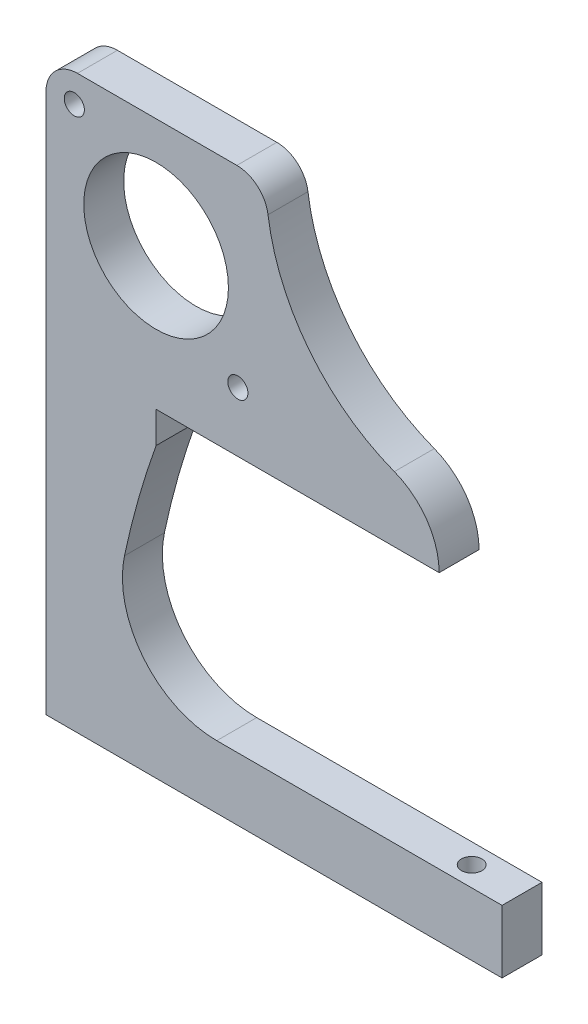
SolidWorks part; units mm, degrees
ref_plane "Front Plane" through (0, 0, 0) normal (0, 0, 1) x (1, 0, 0)
ref_plane "Top Plane" through (0, 0, 0) normal (0, 1, 0) x (1, 0, 0)
ref_plane "Right Plane" through (0, 0, 0) normal (1, 0, 0) x (0, 0, -1)
sketch "Sketch1" plane through (0, 0, 0) normal (0, 0, 1) x (1, 0, 0)
  line L0 (0, 0) -> (35, 0)
  line L1 (62.5, -40) -> (62.5, -43.3792) construction
  line L2 (9.525, -90.8) -> (0, -90.8)
  line L3 (0, -40) -> (0, 0)
  line L4 (30.5, -30.5) -> (4.5, -4.5) construction
  line L5 (4.5, -4.5) -> (30.5, -4.5) construction
  line L6 (4.5, -4.5) -> (4.5, -30.5) construction
  line L7 (4.5, -30.5) -> (30.5, -30.5) construction
  line L8 (30.5, -4.5) -> (30.5, -30.5) construction
  line L9 (0, -40) -> (35, -40) construction
  line L10 (35, -40) -> (35, 0) construction
  line L11 (4.5, -30.5) -> (30.5, -4.5) construction
  line L12 (9.525, -90.8) -> (9.525, -96.7126) construction
  line L13 (0, -90.8) -> (0, -40)
  line L14 (17.5, -40) -> (62.5, -40)
  line L15 (17.5, -40) -> (17.5, -45)
  line L16 (17.5, -45) -> (17.5, -17.5) construction
  line L17 (9.525, -90.8) -> (62.5, -90.8)
  line L18 (62.5, -90.8) -> (62.5, -80.8)
  line L19 (62.5, -80.8) -> (9.8945, -80.8)
  line L20 (62.5, -80.8) -> (72.5, -80.8)
  line L21 (72.5, -80.8) -> (72.5, -90.8)
  line L22 (72.5, -90.8) -> (62.5, -90.8)
  arc A0 (9.8945, -80.8) -> (17.5, -45) centre (145.026, -90.8) cw
  arc A1 (35, 0) -> (55.3806, -29.6446) centre (66.75, 0) ccw
  circle A2 centre (4.5, -4.5) radius 1.6002
  circle A3 centre (17.5, -17.5) radius 11.5
  circle A4 centre (30.5, -30.5) radius 1.6002
  arc A5 (62.5, -40) -> (55.3806, -29.6446) centre (51.4091, -40) ccw
  point P17 (17.5, -17.5)
  dimension "D3" = 3.2004
  dimension "D4" = 40
  dimension "D8" = 23
  dimension "D9" = 31.75
  dimension "D12" = 10
  dimension "D2" = 26
  dimension "D5" = 35
  dimension "D6" = 50.8
  dimension "D7" = 9.525
  dimension "D10" = 5
  dimension "D11" = 45
  dimension "D13" = 10
extrude "Boss-Extrude1" add sketch "Sketch1" along normal blind 6.35 contours L14 A5 A1 L0 L3 L13 L2 L17 L18 L19 A0 L15 A2 A3 A4 region at (17.5, -1.1023, 0)
hole_wizard "#6-32 Tapped Hole1" positions "Sketch4" profile "Sketch3" tap size "#6-32" standard "ANSI Inch"
sketch "Sketch4" plane through (0, -40, 0) normal (0, -1, 0) x (-1, 0, 0)
  line L0 (-17.5, -3.175) -> (-62.5, -3.175) construction
  line L3 (-17.5, -6.35) -> (-17.5, 0) construction
  line L4 (-62.5, -6.35) -> (-62.5, 0) construction
  point P0 (-22.58, -3.175)
  point P2 (-47.98, -3.175)
  dimension "D1" = 5.08
  dimension "D2" = 25.4
sketch "Sketch3" plane through (22.58, -40, 3.175) normal (1, 0, 0) x (0, 0, -1)
  line L0 (0, 0) -> (0, 10.9764)
  line L1 (0, 10.9764) -> (1.625, 10)
  line L2 (1.625, 10) -> (1.625, 0)
  line L5 (1.625, 0) -> (0, 0)
  line L10 (0, 10.9764) -> (-1.625, 10) construction
  line L11 (0, -6.35) -> (0, 107.95) construction
  dimension "Tap Drill Dia." = 3.25
  dimension "Tap Drill Depth" = 10
  dimension "Drill Angle" = 118
cosmetic thread "Rosca de taladro1" parameters "D1"=7.0104, "D2"=4.25
cosmetic thread "Rosca de taladro2" parameters "D1"=7.0104, "D2"=4.25
fillet "Redondeo1" radius 15 1 edges at (9.8945, -80.8, 3.175)
extrude "Saliente-Extruir1" add sketch "Sketch1<4>" along normal blind 6.35 contours L22 L21 L20 L18 region at (67.5, -85.8, 0)
sketch "Sketch1<4>" plane through (0, 0, 0) normal (0, 0, 1) x (1, 0, 0) same geometry as "Sketch1"
sketch "Croquis1" plane through (0, -90.8, 0) normal (0, -1, 0) x (1, 0, 0)
  line L0 (72.5, 3.175) -> (0, 3.175) construction
  line L4 (0, 0) -> (72.5, 0)
  line L5 (72.5, 0) -> (72.5, 6.35)
  line L6 (72.5, 6.35) -> (0, 6.35)
  line L7 (0, 6.35) -> (0, 0)
  line L8 (0, 0) -> (72.5, 0)
  line L9 (72.5, 0) -> (72.5, 6.35)
  line L10 (72.5, 6.35) -> (0, 6.35)
  line L11 (0, 6.35) -> (0, 0)
  circle A0 centre (64.5, 3.175) radius 1.625
  point P6 (64.5, 3.175)
  dimension "D3" = 3.25
  dimension "D2" = 8
  dimension "D1" = 0
extrude "Cortar-Extruir1" cut sketch "Croquis1" against normal up to next contours L0 A0 | A0 L0 region at (64.5, -90.8, 2.4853) region at (64.5, -90.8, 3.8647)
fillet "Redondeo2" radius 5 2 edges at (0, 0, 3.175) (35, 0, 3.175)
